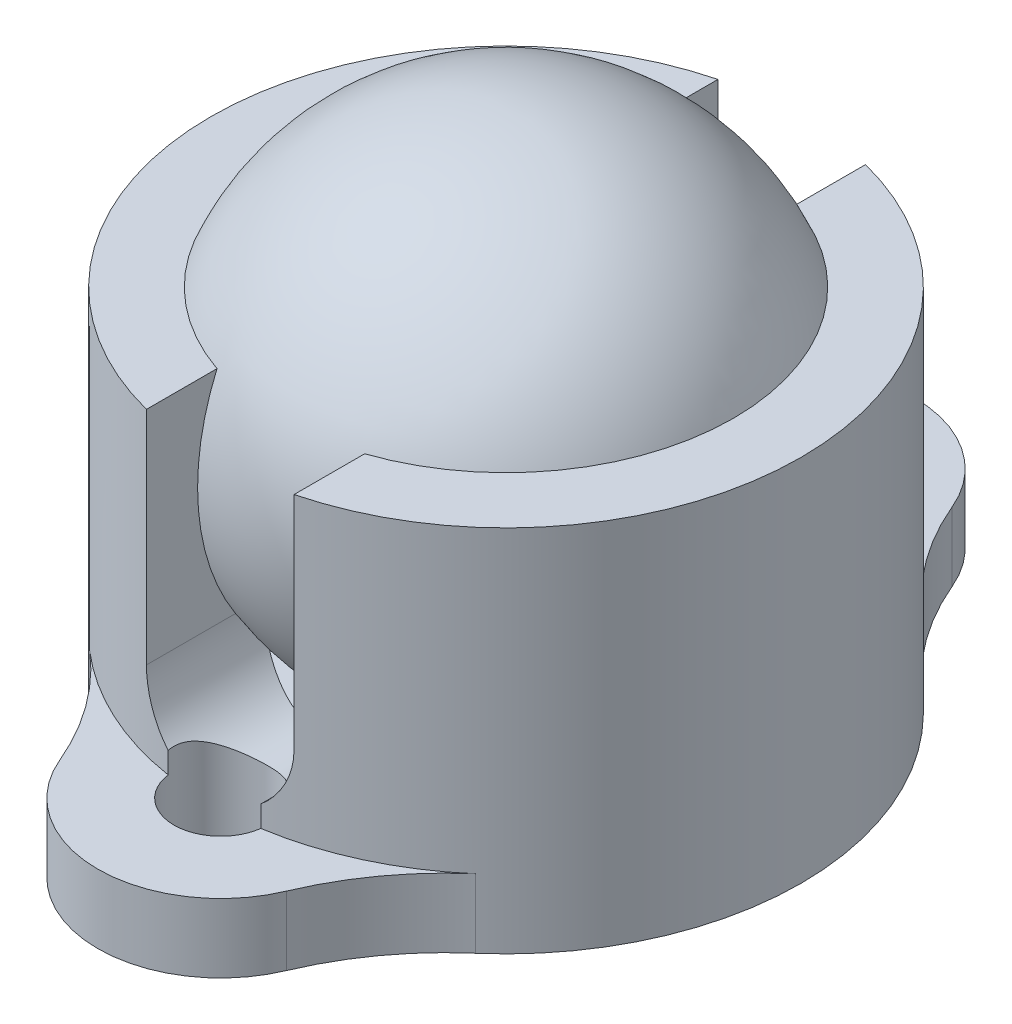
SolidWorks part; units mm, degrees
ref_plane "Front Plane" through (0, 0, 0) normal (0, 0, 1) x (1, 0, 0)
ref_plane "Top Plane" through (0, 0, 0) normal (0, 1, 0) x (1, 0, 0)
ref_plane "Right Plane" through (0, 0, 0) normal (1, 0, 0) x (0, 0, -1)
sketch "Sketch1" plane through (0, 0, 0) normal (0, 1, 0) x (1, 0, 0)
  circle A0 centre (0, 0) radius 7.62
  dimension "D1" = 15.24
extrude "Boss-Extrude1" add sketch "Sketch1" along normal blind 9.525
sketch "Sketch2" plane through (0, 0, 0) normal (0, 0, 1) x (1, 0, 0)
  line L1 (0, 13.462) -> (0, 0.762)
  arc A0 (0, 0.762) -> (0, 13.462) centre (0, 7.112) ccw
  point P1 (0, 0)
  point P4 (0, 13.462)
  dimension "D1" = 12.7
  dimension "D2" = 13.462
ref_axis "Axis1" through (0, 22.0027, 0) along (0, -1, 0)
ref_plane "Plane1" through (0, 0, -7.62) normal (0, 0, -1) x (-1, 0, 0)
sketch "Sketch4" plane through (0, 9.525, 0) normal (0, 1, 0) x (1, 0, 0)
  circle A0 centre (0, 0) radius 4.7625
  dimension "D1" = 9.525
extrude "Cut-Extrude2" cut sketch "Sketch4" against normal blind 7.62 contours A0
sketch "Sketch3" plane through (0, 0, -7.62) normal (0, 0, -1) x (-1, 0, 0)
  line L0 (-1.905, 9.525) -> (-1.905, 3.81)
  line L1 (1.905, 9.525) -> (-1.905, 9.525)
  line L2 (1.905, 9.525) -> (1.905, 3.81)
  line L3 (0, 22.0027) -> (0, -1.0478) construction
  line L4 (7.62, 9.525) -> (-7.62, 9.525) construction
  line L6 (4.7625, 1.905) -> (-4.7625, 1.905) construction
  arc A0 (-1.905, 3.81) -> (1.905, 3.81) centre (0, 3.81) ccw
  point P4 (0, 0)
  point P12 (0, 1.905)
  dimension "D1" = 3.81
extrude "Cut-Extrude1" cut sketch "Sketch3" against normal through all
revolve "Revolve3" add sketch "Sketch2" angle 360 about L1
sketch "Sketch6" plane through (0, 0, 0) normal (0, -1, 0) x (1, 0, 0)
  arc A0 (-4.978, 5.7692) -> (-2.9283, 8.5932) centre (-9.9561, 11.5384) ccw
  circle A1 centre (0, 0) radius 7.62 construction
  arc A2 (-2.9283, 8.5932) -> (2.9283, 8.5932) centre (0, 7.366) cw
  arc A3 (2.9283, 8.5932) -> (4.978, 5.7692) centre (9.9561, 11.5384) ccw
  circle A4 centre (0, 0) radius 7.62 construction
  arc A5 (-2.9283, -8.5932) -> (-4.978, -5.7692) centre (-9.9561, -11.5384) ccw
  arc A6 (2.9283, -8.5932) -> (-2.9283, -8.5932) centre (0, -7.366) cw
  arc A7 (4.978, -5.7692) -> (2.9283, -8.5932) centre (9.9561, -11.5384) ccw
  arc A8 (4.978, 5.7692) -> (4.978, -5.7692) centre (0, 0) cw
  arc A9 (-4.978, 5.7692) -> (-4.978, -5.7692) centre (0, 0) ccw
  point P23 (0, 0)
  point P24 (2.7733, 8.6816)
  point P25 (0, 0)
  point P26 (0, 0)
  point P27 (4.8578, 5.8708)
  point P28 (0, 0)
  point P29 (0, 0)
  dimension "D3" = 3.175
  dimension "D4" = 7.62
  dimension "D1" = 7.366
  dimension "D2" = 2
extrude "Boss-Extrude2" add sketch "Sketch6" against normal blind 1.778
sketch "Sketch5" plane through (0, 0, 0) normal (0, -1, 0) x (1, 0, 0)
  circle A0 centre (0, 7.366) radius 1.2065
  circle A1 centre (0, -7.366) radius 1.2065
  point P5 (0, 0)
  dimension "D3" = 2.413
  dimension "D1" = 14.732
  dimension "D2" = 7.366
extrude "Cut-Extrude3" cut sketch "Sketch5" against normal up to next and the other way through all
